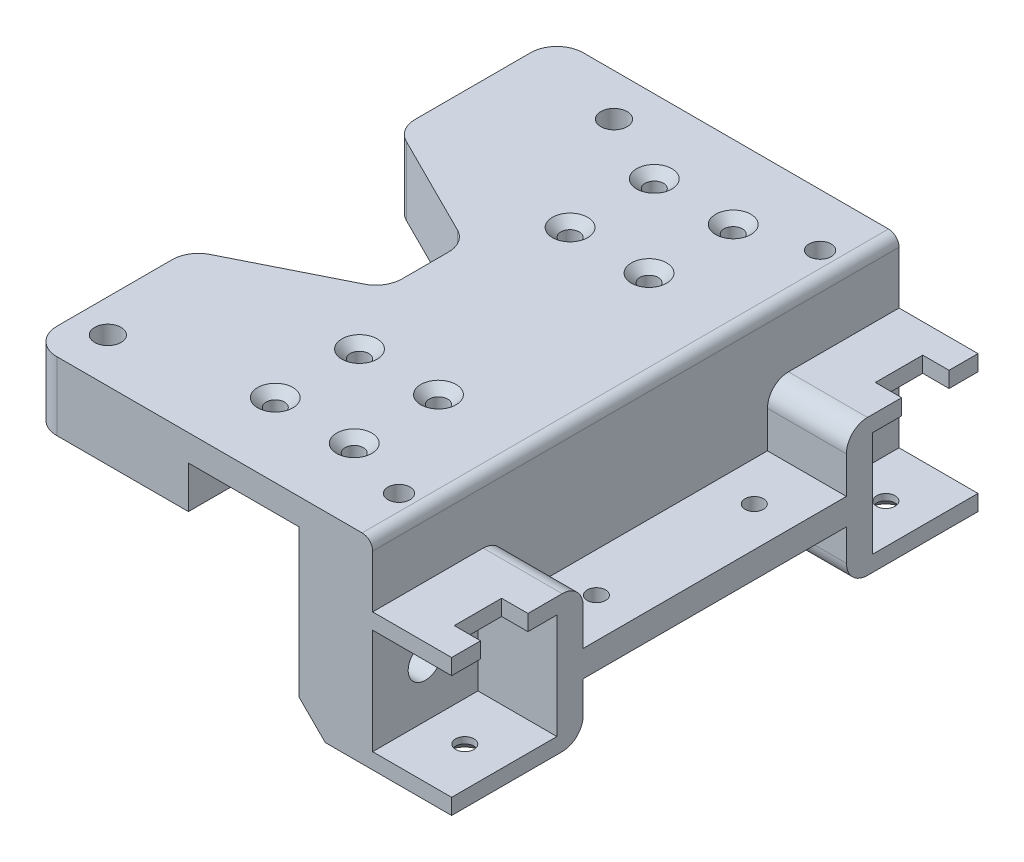
SolidWorks part; units mm, degrees
ref_plane "Front Plane" through (0, 0, 0) normal (0, 0, 1) x (1, 0, 0)
ref_plane "Top Plane" through (0, 0, 0) normal (0, 1, 0) x (1, 0, 0)
ref_plane "Right Plane" through (0, 0, 0) normal (1, 0, 0) x (0, 0, -1)
sketch "Sketch1" plane through (0, 0, 0) normal (0, 1, 0) x (1, 0, 0)
  line L0 (0, 50) -> (0, -50) construction
  line L1 (-10, 50) -> (10, 50)
  line L2 (-10, 50) -> (-10, -50)
  line L3 (-10, -50) -> (10, -50)
  line L4 (10, 50) -> (10, -50) construction
  line L5 (-10, 50) -> (10, -50) construction
  line L6 (-10, -50) -> (10, 50) construction
  line L7 (-7.5, 36) -> (7.5, 36) construction
  line L8 (-7.5, 36) -> (7.5, 20) construction
  line L9 (-10, 0) -> (10, 0) construction
  line L10 (-7.5, -36) -> (7.5, -20) construction
  line L11 (-7.5, -36) -> (7.5, -36) construction
  line L12 (-7.5, 20) -> (7.5, 20) construction
  line L13 (10, 50) -> (11, 50)
  line L14 (11, 50) -> (11, -50)
  line L15 (11, -50) -> (10, -50)
  circle A0 centre (-7.5, 36) radius 1.75
  circle A1 centre (7.5, 36) radius 1.75
  circle A2 centre (-7.5, 20) radius 1.75
  circle A3 centre (7.5, 20) radius 1.75
  circle A4 centre (7.5, -20) radius 1.75
  circle A5 centre (-7.5, -20) radius 1.75
  circle A6 centre (7.5, -36) radius 1.75
  circle A7 centre (-7.5, -36) radius 1.75
  point P0 (0, 0)
  point P16 (0, 36)
  dimension "D2" = 3.5
  dimension "D1" = 20
  dimension "D3" = 15
  dimension "D4" = 16
  dimension "D5" = 100
  dimension "D6" = 20
  dimension "D7" = 1
extrude "Boss-Extrude1" add sketch "Sketch1" along normal blind 5
sketch "Sketch2" plane through (11, 0, 0) normal (1, 0, 0) x (0, 0, -1)
  line L1 (-50, 5) -> (50, 5)
  line L2 (-50, 5) -> (-50, -33)
  line L3 (-50, -33) -> (50, -33)
  line L5 (50, 5) -> (50, -33)
  line L6 (50, 5) -> (50, 0) construction
  line L7 (-50, 5) -> (-50, 0) construction
  line L8 (-50, 5) -> (50, 5) construction
  dimension "D1" = 38
extrude "Boss-Extrude2" add sketch "Sketch2" along normal blind 14
sketch "Sketch3" plane through (25, 0, 0) normal (1, 0, 0) x (0, 0, -1)
  line L0 (0, 5) -> (0, -33) construction
  line L1 (-25, -18) -> (25, -18)
  line L2 (-25, -18) -> (-25, -23)
  line L3 (-25, -23) -> (25, -23)
  line L4 (25, -18) -> (25, -23)
  line L5 (50, 5) -> (-50, 5) construction
  line L6 (-50, -33) -> (50, -33) construction
  point P10 (0, -18)
  dimension "D1" = 5
  dimension "D2" = 50
  dimension "D3" = 10
extrude "Boss-Extrude3" add sketch "Sketch3" along normal blind 15
sketch "Sketch4" plane through (0, -18, 0) normal (0, 1, 0) x (1, 0, 0)
  line L0 (25, 0) -> (40, 0) construction
  line L1 (25, 25) -> (25, -25) construction
  line L2 (40, 25) -> (40, -25) construction
  line L3 (32.5, -15) -> (32.5, 15) construction
  circle A0 centre (32.5, 15) radius 1.75
  circle A1 centre (32.5, -15) radius 1.75
  point P8 (32.5, 0)
  dimension "D1" = 30
  dimension "D2" = 3.5
extrude "Cut-Extrude1" cut sketch "Sketch4" against normal through all
sketch "Sketch8" plane through (25, 0, 0) normal (1, 0, 0) x (0, 0, -1)
  line L0 (-50, 5) -> (-50, -33) construction
  line L1 (-50, -7) -> (-25, -7)
  line L2 (-50, -7) -> (-50, -10)
  line L3 (-50, -33) -> (-25, -33)
  line L4 (-25, -7) -> (-25, -33)
  line L5 (-50, -30) -> (-50, -33)
  line L6 (-50, -30) -> (-30, -30)
  line L8 (-50, -10) -> (-30, -10)
  line L9 (-30, -30) -> (-30, -10)
  line L10 (0, 20.9) -> (0, -20.9) construction
  line L11 (30, -30) -> (30, -10)
  line L12 (50, -10) -> (30, -10)
  line L13 (50, -30) -> (30, -30)
  line L14 (50, -30) -> (50, -33)
  line L15 (25, -7) -> (25, -33)
  line L16 (50, -33) -> (25, -33)
  line L17 (50, -7) -> (50, -10)
  line L18 (50, -7) -> (25, -7)
  line L19 (-50, -33) -> (50, -33) construction
  dimension "D1" = 3
  dimension "D2" = 5
  dimension "D3" = 3
  dimension "D4" = 20
  dimension "D5" = 20
extrude "Boss-Extrude6" add sketch "Sketch8" along normal blind 15
sketch "Sketch9" plane through (25, 0, 0) normal (1, 0, 0) x (0, 0, -1)
  line L0 (-50, -10) -> (-30, -30) construction
  line L1 (50, -10) -> (30, -30) construction
  circle A0 centre (-40, -20) radius 3.25
  circle A1 centre (40, -20) radius 3.25
  dimension "D1" = 6.5
extrude "Cut-Extrude3" cut sketch "Sketch9" against normal through all
sketch "Sketch10" plane through (11, 0, 0) normal (-1, 0, 0) x (0, 0, 1)
  circle A0 centre (-40, -20) radius 5.25
  circle A1 centre (40, -20) radius 5.25
  dimension "D1" = 10.5
extrude "Cut-Extrude4" cut sketch "Sketch10" against normal offset from surface (9 mm away) 5 up to face at (25, -20, 36.75)
sketch "Sketch11" plane through (0, -7, 0) normal (0, 1, 0) x (1, 0, 0)
  line L0 (40, -25) -> (40, -50) construction
  line L1 (40, -35.5) -> (35, -35.5)
  line L2 (40, -35.5) -> (40, -44.5)
  line L3 (40, -44.5) -> (35, -44.5)
  line L4 (35, -35.5) -> (35, -44.5)
  line L5 (35, -40) -> (40, -40) construction
  line L6 (40, -50) -> (25, -50) construction
  line L7 (-10, 0) -> (40, 0) construction
  line L8 (-10, 50) -> (-10, -50) construction
  line L9 (40, 25) -> (40, -25) construction
  line L10 (40, -35.5) -> (35, -35.5)
  line L11 (40, -44.5) -> (35, -44.5)
  line L12 (35, 40) -> (40, 40) construction
  line L13 (40, 44.5) -> (35, 44.5)
  line L14 (40, 35.5) -> (35, 35.5)
  line L15 (35, 35.5) -> (35, 44.5)
  line L16 (40, 44.5) -> (35, 44.5)
  line L17 (40, 35.5) -> (40, 44.5)
  line L18 (40, 35.5) -> (35, 35.5)
  line M7 (40, -50) -> (40, -25)
  dimension "D1" = 9
  dimension "D2" = 10
  dimension "D3" = 5
extrude "Cut-Extrude5" cut sketch "Sketch11" against normal up to next contours L1 L4 L3 M7 | L14 L17 L13 L15 region at (37.5, -7, 40) region at (37.5, -7, -40)
sketch "Sketch12" plane through (0, -30, 0) normal (0, 1, 0) x (1, 0, 0)
  line L0 (40, -40) -> (25, -40) construction
  line L1 (40, -30) -> (40, -50) construction
  line L2 (25, -25) -> (25, -50) construction
  line L3 (-20.9, 0) -> (20.9, 0) construction
  circle A0 centre (32.5, -40) radius 1.75
  circle A2 centre (32.5, 40) radius 1.75
  dimension "D1" = 3.5
extrude "Cut-Extrude6" cut sketch "Sketch12" against normal through all
sketch "Sketch13" plane through (-10, 0, 0) normal (-1, 0, 0) x (0, 0, 1)
  line L1 (-50, 5) -> (50, 5)
  line L2 (-50, 5) -> (-50, -8)
  line L3 (-50, -8) -> (50, -8)
  line L4 (50, 5) -> (50, -8)
  dimension "D1" = 13
extrude "Boss-Extrude7" add sketch "Sketch13" along normal blind 30
sketch "Sketch14" plane through (0, 5, 0) normal (0, 1, 0) x (1, 0, 0)
  line L6 (-27.65, 42) -> (-27.65, -41.58) construction
  line L12 (-21.15, 35.5) -> (40, 35.5) construction
  line L18 (-33.73, -35.5) -> (40, -35.5) construction
  circle A0 centre (-21.15, 42) radius 2.5
  circle A1 centre (-33.73, -41.58) radius 2.5
  circle A2 centre (-33.73, -41.58) radius 6.08 construction
  circle A3 centre (-21.15, 42) radius 6.5 construction
  dimension "D1" = 5
  dimension "D2" = 5
  dimension "D4" = 12.16
  dimension "D5" = 13
  dimension "D3" = 21.15
extrude "Cut-Extrude7" cut sketch "Sketch14" against normal through all
sketch "Sketch15" plane through (0, -8, 0) normal (0, -1, 0) x (1, 0, 0)
  line L0 (-40, -50) -> (-40, 50) construction
  line L1 (-29.63, 43.9471) -> (-33.73, 46.3143)
  line L2 (-33.73, 46.3143) -> (-37.83, 43.9471)
  line L3 (-37.83, 43.9471) -> (-37.83, 39.2129)
  line L4 (-37.83, 39.2129) -> (-33.73, 36.8457)
  line L5 (-33.73, 36.8457) -> (-29.63, 39.2129)
  line L6 (-29.63, 39.2129) -> (-29.63, 43.9471)
  line L7 (-17.05, -44.3671) -> (-17.05, -39.6329)
  line L8 (-17.05, -39.6329) -> (-21.15, -37.2657)
  line L9 (-21.15, -37.2657) -> (-25.25, -39.6329)
  line L10 (-25.25, -39.6329) -> (-25.25, -44.3671)
  line L11 (-25.25, -44.3671) -> (-21.15, -46.7343)
  line L12 (-21.15, -46.7343) -> (-17.05, -44.3671)
  circle A0 centre (-33.73, 41.58) radius 4.1 construction
  circle A1 centre (-21.15, -42) radius 4.1 construction
  dimension "D1" = 8.2
extrude "Cut-Extrude8" cut sketch "Sketch15" against normal blind 5
sketch "Sketch16" plane through (0, 5, 0) normal (0, 1, 0) x (1, 0, 0)
  line L0 (20, 40) -> (40, 40) construction
  line L1 (40, 40) -> (40, -40) construction
  line L2 (40, -40) -> (20, -40) construction
  line L3 (20, -40) -> (20, 40) construction
  line L4 (40, 50) -> (40, 30) construction
  line L5 (40, -30) -> (40, -50) construction
  circle A0 centre (20, 40) radius 2.1
  circle A1 centre (20, -40) radius 2.1
  dimension "D1" = 4.2
  dimension "D2" = 4.2
  dimension "D3" = 20
extrude "Cut-Extrude9" cut sketch "Sketch16" against normal blind 4
chamfer "Chamfer1" distance 1.6 angle 45 8 edges at (7.5, 5, 34.25) (-7.5, 5, 34.25) (7.5, 5, 18.25) (-7.5, 5, 18.25) (7.5, 5, -18.25) (-7.5, 5, -18.25) (7.5, 5, -34.25) (-7.5, 5, -34.25)
sketch "Sketch17" plane through (0, 5, 0) normal (0, 1, 0) x (1, 0, 0)
  line L0 (-40, 20) -> (-15, 7.5)
  line L1 (-40, -50) -> (-40, 50) construction
  line L2 (-15, 7.5) -> (-15, -7.5)
  line L3 (-15, -7.5) -> (-40, -20)
  line L4 (-40, -20) -> (-40, 20)
  point P5 (-15, 0)
  dimension "D1" = 15
  dimension "D2" = 25
  dimension "D3" = 40
extrude "Cut-Extrude10" cut sketch "Sketch17" against normal through all
chamfer "Chamfer2" distance 1.8 angle 45 2 edges at (32.5, -33, -41.75) (32.5, -33, 41.75)
chamfer "Chamfer3" distance 5 angle 45 1 edges at (11, -33, 0)
sketch "Sketch18" plane through (0, 1, 0) normal (0, 1, 0) x (1, 0, 0)
  circle A0 centre (20, 40) radius 1.75
  circle A1 centre (20, -40) radius 1.75
  dimension "D1" = 3.5
  dimension "D2" = 3.5
extrude "Cut-Extrude11" cut sketch "Sketch18" against normal blind 4
fillet "Fillet1" radius 5 6 edges at (-40, -1.5, 50) (-40, -1.5, 20) (-15, -1.5, 7.5) (-15, -1.5, -7.5) (-40, -1.5, -20) (-40, -1.5, -50)
fillet "Fillet2" radius 4 4 edges at (32.5, -33, -25) (32.5, -7, -25) (32.5, -33, 25) (32.5, -7, 25)
fillet "Fillet3" radius 2 1 edges at (25, 5, 0)
